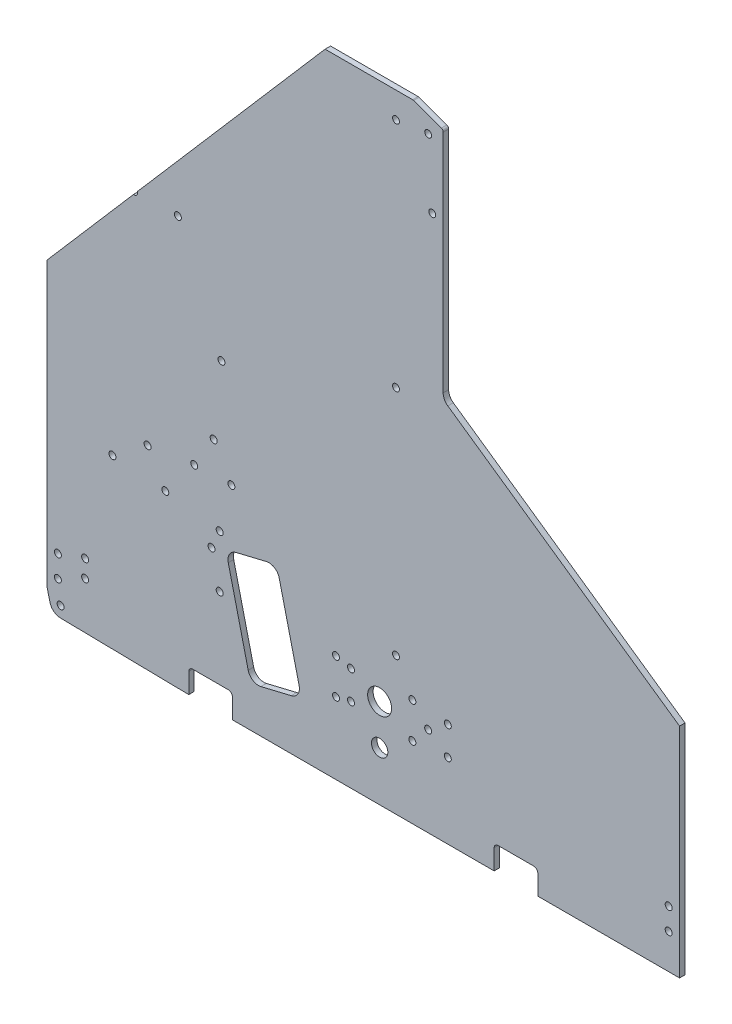
SolidWorks part; units mm, degrees
ref_plane "Front Plane" through (0, 0, 0) normal (0, 0, 1) x (1, 0, 0)
ref_plane "Top Plane" through (0, 0, 0) normal (0, 1, 0) x (1, 0, 0)
ref_plane "Right Plane" through (0, 0, 0) normal (1, 0, 0) x (0, 0, -1)
sketch "Sketch1" plane through (0, 0, 0) normal (0, 0, 1) x (1, 0, 0)
  line L0 (82.55, -20.32) -> (82.55, -6.35)
  line L2 (0, 0) -> (0, 157.48)
  line L4 (368.3, -20.32) -> (368.3, 106.68)
  line L5 (82.55, -6.35) -> (107.95, -6.35)
  line L6 (107.95, -6.35) -> (107.95, -20.32)
  line L7 (107.95, -20.32) -> (260.35, -20.32)
  line L8 (260.35, -20.32) -> (260.35, -6.35)
  line L9 (260.35, -6.35) -> (285.75, -6.35)
  line L10 (285.75, -6.35) -> (285.75, -20.32)
  line L11 (285.75, -20.32) -> (368.3, -20.32)
  line L12 (361.95, 12.7) -> (368.3, 12.7) construction
  line L13 (0, 0) -> (6.35, 0) construction
  line L14 (0.1896, -7.8901) -> (1.7771, -14.2401)
  line L15 (7.8295, -19.0491) -> (82.55, -20.32)
  line L16 (0, 0) -> (0, -6.35)
  line L17 (85.725, 97.155) -> (82.9754, 95.5675) construction
  line L18 (97.0634, 115.6163) -> (58.5686, 93.3913) construction
  line L19 (97.0634, 115.6163) -> (107.3822, 97.7437) construction
  line L20 (58.5686, 93.3913) -> (68.8873, 75.5187) construction
  line L21 (107.3822, 97.7437) -> (68.8873, 75.5187) construction
  line L22 (97.0634, 115.6163) -> (68.8873, 75.5187) construction
  line L23 (58.5686, 93.3913) -> (107.3822, 97.7437) construction
  line L24 (7.9375, -12.7) -> (95.7973, 60.4105) construction
  line L25 (203.2, 59.805) -> (203.2, 194.805) construction
  line L26 (203.2, 194.805) -> (203.2, 329.805) construction
  line L27 (355.6, 332.105) -> (330.2, 332.105) construction
  line L28 (330.2, 332.105) -> (330.2, 217.805) construction
  line L29 (330.2, 217.805) -> (355.6, 217.805) construction
  line L30 (355.6, 217.805) -> (355.6, 332.105) construction
  line L31 (203.2, 344.805) -> (203.2, 194.805) construction
  line L32 (50.8, 332.105) -> (76.2, 332.105) construction
  line L33 (76.2, 332.105) -> (76.2, 217.805) construction
  line L34 (50.8, 217.805) -> (50.8, 332.105) construction
  line L35 (76.2, 217.805) -> (50.8, 217.805) construction
  line L36 (213.2, 344.805) -> (230.6638, 338.455)
  line L37 (203.2, 344.805) -> (161.925, 344.805)
  line L38 (203.2, 344.805) -> (213.2, 344.805)
  line L39 (348.5362, 344.805) -> (413.4623, 344.805)
  line L40 (348.5362, 344.805) -> (230.6638, 344.805) construction
  line L42 (161.925, 344.805) -> (0, 157.48)
  line L44 (230.6638, 338.455) -> (230.6638, 202.565)
  line L45 (230.6638, 202.565) -> (368.3, 106.68)
  line L46 (213.2, 344.805) -> (-141.0713, 344.805) construction
  circle A0 centre (6.35, 0) radius 2.032
  circle A1 centre (6.35, 12.7) radius 2.032
  circle A2 centre (361.95, 0) radius 2.032
  circle A3 centre (361.95, 12.7) radius 2.032
  arc A5 (1.7771, -14.2401) -> (7.8295, -19.0491) centre (7.9375, -12.7) ccw
  circle A6 centre (7.9375, -12.7) radius 2.032
  arc A7 (0, -6.35) -> (0.1896, -7.8901) centre (6.35, -6.35) ccw
  circle A8 centre (38.1, 78.105) radius 2.032
  circle A9 centre (85.725, 97.155) radius 2.032
  circle A10 centre (58.5686, 93.3913) radius 2.032
  circle A11 centre (68.8873, 75.5187) radius 2.032
  circle A12 centre (107.3822, 97.7437) radius 2.032
  circle A13 centre (97.0634, 115.6163) radius 2.032
  circle A14 centre (95.7973, 60.4105) radius 2.032
  circle A15 centre (203.2, 59.805) radius 2
  circle A16 centre (203.2, 194.805) radius 2
  circle A17 centre (203.2, 329.805) radius 2
  circle A18 centre (63.5, 313.055) radius 2.032
  circle A19 centre (101.6, 157.48) radius 2.032
  circle A20 centre (355.6, 332.105) radius 2.032
  circle A21 centre (330.2, 332.105) radius 2.032
  circle A22 centre (355.6, 217.805) radius 2.032
  circle A23 centre (330.2, 217.805) radius 2.032
  circle A24 centre (50.8, 332.105) radius 2.032
  circle A25 centre (76.2, 332.105) radius 2.032
  circle A26 centre (50.8, 217.805) radius 2.032
  circle A27 centre (76.2, 217.805) radius 2.032
  circle A28 centre (221.9319, 332.105) radius 2
  circle A29 centre (224.3138, 293.243) radius 2.032
  point P82 (203.2, 344.805)
  point P83 (221.9319, 341.63)
  dimension "D6" = 4.064
  dimension "D10" = 6.35
  dimension "D11" = 4.064
  dimension "D17" = 38.1
  dimension "D27" = 4
  dimension "D31" = 4.064
  dimension "D32" = 41.275
  dimension "D36" = 4.064
  dimension "D47" = 45.212
  dimension "D48" = 4.064
  dimension "D2" = 127
  dimension "D3" = 13.97
  dimension "D4" = 25.4
  dimension "D5" = 152.4
  dimension "D7" = 12.7
  dimension "D8" = 6.35
  dimension "D9" = 20.32
  dimension "D12" = 12.7
  dimension "D13" = 1.5875
  dimension "D14" = 82.55
  dimension "D15" = 368.3
  dimension "D16" = 6.35
  dimension "D18" = 98.425
  dimension "D19" = 47.625
  dimension "D20" = 19.05
  dimension "D21" = 3.175
  dimension "D22" = 60
  dimension "D23" = 20.6375
  dimension "D24" = 44.45
  dimension "D25" = 38.1
  dimension "D26" = 114.3
  dimension "D28" = 135
  dimension "D29" = 12.7
  dimension "D30" = 15
  dimension "D33" = 63.5
  dimension "D34" = 27.4638
  dimension "D35" = 101.6
  dimension "D37" = 114.3
  dimension "D38" = 25.4
  dimension "D39" = 12.7
  dimension "D40" = 157.48
  dimension "D41" = 142.24
  dimension "D42" = 365.125
  dimension "D43" = 10
  dimension "D44" = 6.35
  dimension "D45" = 31.75
  dimension "D46" = 6.35
  dimension "D49" = 6.35
  dimension "D50" = 203.2
extrude "Boss-Extrude1" add sketch "Sketch1" along normal blind 3.175 contours L16 A7 L14 A5 L15 L2 A0 A1 A6 region at (171.4139, 119.6697, 0)
fillet "Fillet1" radius 2.286 4 edges at (285.75, -6.35, 1.5875) (107.95, -6.35, 1.5875) (260.35, -6.35, 1.5875) (82.55, -6.35, 1.5875)
fillet "Fillet2" radius 6.35 1 edges at (230.6638, 202.565, 1.5875)
sketch "Sketch2" plane through (0, 0, 0) normal (0, 0, -1) x (-1, 0, 0)
  circle A0 centre (-100.5528, 71.086) radius 2.032 construction
  circle A1 centre (-100.5528, 40.606) radius 2.032 construction
  circle A2 centre (-22.225, 18.2025) radius 2.032 construction
  circle A3 centre (-22.225, 8.0425) radius 2.032 construction
  circle A4 centre (-100.5528, 71.086) radius 2.032
  circle A5 centre (-100.5528, 40.606) radius 2.032
  circle A6 centre (-22.225, 18.2025) radius 2.032
  circle A7 centre (-22.225, 8.0425) radius 2.032
extrude "Cut-Extrude1" cut sketch "Sketch2" against normal through all
fillet "Fillet3" radius 1.5875 2 edges at (230.6638, 338.455, 1.5875) (213.2, 344.805, 1.5875)
sketch "Sketch3" plane through (0, 0, 3.175) normal (0, 0, 1) x (1, 0, 0)
  line L0 (132.9524, 63.2646) -> (132.7215, 64.2281) construction
  line L1 (128.3814, 66.8897) -> (110.6828, 62.6472) construction
  line L2 (114.5132, 58.4237) -> (126.8822, 61.3887) construction
  line L3 (108.0212, 58.3071) -> (108.2522, 57.3436) construction
  line L4 (131.2006, 57.703) -> (140.0164, 20.9265) construction
  line L5 (144.0993, 16.7636) -> (132.9524, 63.2646) construction
  line L6 (108.2522, 57.3436) -> (119.3991, 10.8426) construction
  line L7 (121.1509, 16.4042) -> (112.3351, 53.1807) construction
  line L8 (119.3991, 10.8426) -> (119.6301, 9.8791) construction
  line L9 (144.3303, 15.8001) -> (144.0993, 16.7636) construction
  line L10 (137.8383, 15.6835) -> (125.4694, 12.7185) construction
  line L11 (123.9701, 7.2175) -> (141.6687, 11.4601) construction
  line L12 (132.9524, 63.2646) -> (132.7215, 64.2281)
  line L13 (128.3814, 66.8897) -> (110.6828, 62.6472)
  line L14 (114.5132, 58.4237) -> (126.8822, 61.3887)
  line L15 (108.0212, 58.3071) -> (108.2522, 57.3436)
  line L16 (131.2006, 57.703) -> (140.0164, 20.9265)
  line L17 (144.0993, 16.7636) -> (132.9524, 63.2646)
  line L18 (108.2522, 57.3436) -> (119.3991, 10.8426)
  line L19 (121.1509, 16.4042) -> (112.3351, 53.1807)
  line L20 (119.3991, 10.8426) -> (119.6301, 9.8791)
  line L21 (144.3303, 15.8001) -> (144.0993, 16.7636)
  line L22 (137.8383, 15.6835) -> (125.4694, 12.7185)
  line L23 (123.9701, 7.2175) -> (141.6687, 11.4601)
  line L24 (127.7894, 69.3598) -> (110.0908, 65.1172)
  line L25 (105.5512, 57.715) -> (105.7822, 56.7515)
  line L26 (105.7822, 56.7515) -> (116.9291, 10.2505)
  line L27 (116.9291, 10.2505) -> (117.16, 9.287)
  line L28 (124.5622, 4.7475) -> (142.2608, 8.99)
  line L29 (146.8003, 16.3922) -> (146.5694, 17.3557)
  line L30 (146.5694, 17.3557) -> (135.4225, 63.8567)
  line L31 (135.4225, 63.8567) -> (135.1915, 64.8202)
  arc A0 (132.7215, 64.2281) -> (128.6308, 66.9403) centre (129.2206, 63.3889) ccw construction
  arc A1 (110.6828, 62.6472) -> (110.4377, 62.5791) centre (111.522, 59.1463) ccw construction
  arc A2 (128.6308, 66.9403) -> (128.3814, 66.8897) centre (129.2206, 63.3889) ccw construction
  arc A3 (110.4377, 62.5791) -> (108.0212, 58.3071) centre (111.522, 59.1463) ccw construction
  arc A4 (119.6301, 9.8791) -> (123.7207, 7.1669) centre (123.1309, 10.7183) ccw construction
  arc A5 (141.9139, 11.5281) -> (144.3303, 15.8001) centre (140.8295, 14.9609) ccw construction
  arc A6 (141.6687, 11.4601) -> (141.9139, 11.5281) centre (140.8295, 14.9609) ccw construction
  arc A7 (123.7207, 7.1669) -> (123.9701, 7.2175) centre (123.1309, 10.7183) ccw construction
  arc A8 (132.7215, 64.2281) -> (128.6308, 66.9403) centre (129.2206, 63.3889) ccw
  arc A9 (110.6828, 62.6472) -> (110.4377, 62.5791) centre (111.522, 59.1463) ccw
  arc A10 (128.6308, 66.9403) -> (128.3814, 66.8897) centre (129.2206, 63.3889) ccw
  arc A11 (110.4377, 62.5791) -> (108.0212, 58.3071) centre (111.522, 59.1463) ccw
  arc A12 (119.6301, 9.8791) -> (123.7207, 7.1669) centre (123.1309, 10.7183) ccw
  arc A13 (141.9139, 11.5281) -> (144.3303, 15.8001) centre (140.8295, 14.9609) ccw
  arc A14 (141.6687, 11.4601) -> (141.9139, 11.5281) centre (140.8295, 14.9609) ccw
  arc A15 (123.7207, 7.1669) -> (123.9701, 7.2175) centre (123.1309, 10.7183) ccw
  arc A16 (110.0908, 65.1172) -> (109.6726, 65.0012) centre (111.522, 59.1463) ccw
  arc A17 (109.6726, 65.0012) -> (105.5512, 57.715) centre (111.522, 59.1463) ccw
  arc A18 (117.16, 9.287) -> (124.1369, 4.6613) centre (123.1309, 10.7183) ccw
  arc A19 (124.1369, 4.6613) -> (124.5622, 4.7475) centre (123.1309, 10.7183) ccw
  arc A20 (142.2608, 8.99) -> (142.6789, 9.1061) centre (140.8295, 14.9609) ccw
  arc A21 (142.6789, 9.1061) -> (146.8003, 16.3922) centre (140.8295, 14.9609) ccw
  arc A22 (135.1915, 64.8202) -> (128.2147, 69.446) centre (129.2206, 63.3889) ccw
  arc A23 (128.2147, 69.446) -> (127.7894, 69.3598) centre (129.2206, 63.3889) ccw
  ellipse E0 centre (124.5974, 48.8487) end of major axis (128.5376, 61.3578) minor radius 6 (131.2006, 57.703) -> (126.8822, 61.3887) ccw construction
  ellipse E1 centre (122.2349, 48.2824) end of major axis (113.0518, 57.6456) minor radius 6 (114.5132, 58.4237) -> (112.3351, 53.1807) ccw construction
  ellipse E2 centre (127.7541, 25.2585) end of major axis (131.6942, 37.7675) minor radius 6 (121.1509, 16.4042) -> (125.4694, 12.7185) ccw construction
  ellipse E3 centre (130.1166, 25.8248) end of major axis (139.2998, 16.4616) minor radius 6 (137.8383, 15.6835) -> (140.0164, 20.9265) ccw construction
  ellipse E4 centre (124.5974, 48.8487) end of major axis (128.5376, 61.3578) minor radius 6 (131.2006, 57.703) -> (126.8822, 61.3887) ccw
  ellipse E5 centre (122.2349, 48.2824) end of major axis (131.4181, 38.9192) minor radius 6 (114.5132, 58.4237) -> (112.3351, 53.1807) ccw
  ellipse E6 centre (127.7541, 25.2585) end of major axis (123.8139, 12.7495) minor radius 6 (121.1509, 16.4042) -> (125.4694, 12.7185) ccw
  ellipse E7 centre (130.1166, 25.8248) end of major axis (139.2998, 16.4616) minor radius 6 (137.8383, 15.6835) -> (140.0164, 20.9265) ccw
  dimension "D1" = 2.54
extrude "Cut-Extrude2" cut sketch "Sketch3" against normal through all contours A22 A23 L24 A16 A17 L25 L26 L27 A18 A19 L28 A20 A21 L29 L30 L31 A15 A12 L20 L18 L15 A11 A9 L13 A10 A8 L12 L17 L21 A13 A14 L23 | A12 A15 L23 A14 A13 L21 L17 L12 A8 A10 L13 A9 A11 L15 L18 L20 E7 L22 E6 L19 E5 L14 E4 L16 | L22 E7 L16 E4 L14 E5 L19 E6 region at (137.844, 39.8506, 3.175) region at (126.1758, 37.0536, 3.175) region at (128.1544, 68.6507, 3.175)
sketch "Sketch4" plane through (0, 0, 3.175) normal (0, 0, 1) x (1, 0, 0)
  line L0 (107.3822, 97.7437) -> (68.8873, 75.5187) construction
  line L1 (168.275, 21.4312) -> (212.725, 21.4312) construction
  line L2 (168.275, 21.4312) -> (168.275, 42.0687) construction
  line L3 (168.275, 42.0687) -> (212.725, 42.0687) construction
  line L4 (212.725, 21.4312) -> (212.725, 42.0687) construction
  line L5 (168.275, 21.4312) -> (212.725, 42.0687) construction
  line L6 (168.275, 42.0687) -> (212.725, 21.4312) construction
  line L7 (97.0634, 115.6163) -> (107.3822, 97.7437) construction
  line L8 (107.95, -20.32) -> (260.35, -20.32) construction
  line L9 (193.675, 31.75) -> (177.005, 31.75) construction
  line L10 (190.5, 31.75) -> (193.675, 31.75) construction
  line L11 (6.35, 12.7) -> (361.95, 12.7) construction
  line L12 (107.95, -6.35) -> (107.95, -20.32) construction
  line L13 (193.675, 31.75) -> (220.6625, 31.75) construction
  line L14 (177.005, 23.4569) -> (177.005, 40.0431) construction
  line L15 (213.2, 44.805) -> (193.2, 44.805) construction
  line L16 (213.2, 44.805) -> (213.2, 344.805) construction
  line L17 (213.2, 344.805) -> (193.2, 344.805) construction
  line L18 (193.2, 44.805) -> (193.2, 344.805) construction
  line L19 (213.2, 44.805) -> (193.2, 344.805) construction
  line L20 (213.2, 344.805) -> (193.2, 44.805) construction
  line L21 (226.9319, 332.105) -> (226.9319, 31.75) construction
  line L22 (237.33, 40.0431) -> (233.3612, 40.0431) construction
  line L23 (237.33, 23.4569) -> (233.3612, 23.4569) construction
  circle A0 centre (168.275, 42.0687) radius 2.032
  circle A1 centre (212.725, 42.0687) radius 2.032
  circle A2 centre (212.725, 21.4312) radius 2.032
  circle A3 centre (168.275, 21.4312) radius 2.032
  circle A4 centre (193.675, 31.75) radius 6.985
  circle A7 centre (220.6625, 31.75) radius 14.2875 construction
  circle A8 centre (193.675, 31.75) radius 12.7 construction
  circle A9 centre (177.005, 40.0431) radius 2.032
  circle A10 centre (177.005, 23.4569) radius 2.032
  circle A11 centre (237.33, 40.0431) radius 2.032 construction
  circle A12 centre (237.33, 23.4569) radius 2.032 construction
  circle A13 centre (193.675, 8.4667) radius 4.7625
  circle A14 centre (221.9319, 31.75) radius 2.032
  circle A15 centre (221.9319, 31.75) radius 5 construction
  circle A16 centre (221.9319, 332.105) radius 5 construction
  circle A17 centre (233.3612, 23.4569) radius 2.032
  circle A18 centre (233.3612, 40.0431) radius 2.032
  point P0 (190.5, 31.75)
  point P26 (203.2, 194.805)
  point P38 (177.005, 31.75)
  dimension "D1" = 4.064
  dimension "D4" = 13.97
  dimension "D7" = 9.525
  dimension "D10" = 25.4
  dimension "D11" = 28.575
  dimension "D16" = 10
  dimension "D17" = 4.064
  dimension "D18" = 10
  dimension "D2" = 52.07
  dimension "D3" = 3.175
  dimension "D5" = 82.55
  dimension "D6" = 26.9875
  dimension "D8" = 20
  dimension "D9" = 300
  dimension "D12" = 16.67
  dimension "D13" = 16.5862
  dimension "D14" = 60.325
  dimension "D15" = 23.2833
  dimension "D19" = 3.9688
extrude "Cut-Extrude3" cut sketch "Sketch4" against normal through all
